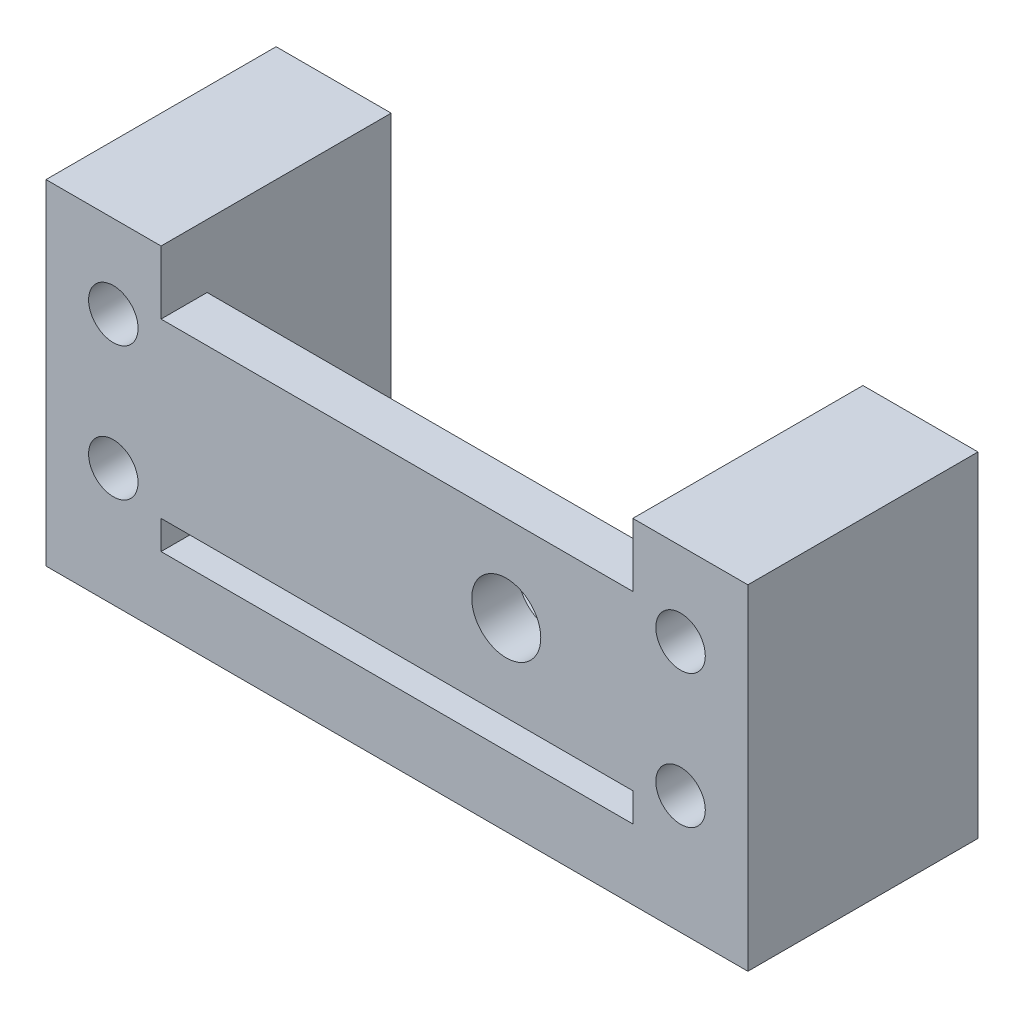
SolidWorks part; units mm, degrees
ref_plane "Спереди" through (0, 0, 0) normal (0, 0, 1) x (1, 0, 0)
ref_plane "Сверху" through (0, 0, 0) normal (0, 1, 0) x (1, 0, 0)
ref_plane "Справа" through (0, 0, 0) normal (1, 0, 0) x (0, 0, -1)
sketch "Эскиз1" plane through (0, 0, 0) normal (0, 0, 1) x (1, 0, 0)
  line L2 (-61.1906, -40.1769) -> (-61.1906, -15.0857)
  line L3 (-61.1906, -15.0857) -> (-51.1906, -15.0857)
  line L4 (-0.1906, -38.0857) -> (-0.1906, -15.0857)
  line L8 (-0.1906, -15.0857) -> (-10.1906, -15.0857)
  line L9 (-10.1906, -15.0857) -> (-10.1906, -38.0857)
  line L10 (-51.1906, -15.0857) -> (-51.1906, -38.0857)
  line L11 (-51.1906, -38.0857) -> (-10.1906, -38.0857)
  line L12 (-61.1906, -40.1769) -> (-61.1906, -44.1769)
  line L13 (-61.1906, -44.1769) -> (-0.1906, -44.1769)
  line L14 (-0.1906, -44.1769) -> (-0.1906, -38.0857)
  point P0 (0, 0)
extrude "Бобышка-Вытянуть1" add sketch "Эскиз1" along normal blind 20
sketch "Эскиз3" plane through (-61.1906, 0, 0) normal (-1, 0, 0) x (0, 0, 1)
  line L5 (0, -15.0857) -> (0, -44.1769) construction
  line L6 (15, -15.0857) -> (0, -15.0857) construction
  line L7 (15, -15.0857) -> (15, -38.2478) construction
  line L8 (15, -38.2478) -> (0, -38.2478) construction
  line L9 (0, -15.0857) -> (0, -38.2478) construction
  point P7 (0, 0)
sketch "Эскиз5" plane through (0, 0, 20) normal (0, 0, 1) x (1, 0, 0)
  line L0 (-51.1906, -38.0857) -> (-51.1906, -15.0857) construction
  line L1 (-10.1906, -28.0857) -> (-24.1906, -28.0857) construction
  line L12 (-10.1906, -38.0857) -> (-51.1906, -38.0857) construction
  line L13 (-10.1906, -38.0857) -> (-10.1906, -18.0857) construction
  line L14 (-10.1906, -18.0857) -> (-51.1906, -18.0857) construction
  line L15 (-51.1906, -38.0857) -> (-51.1906, -18.0857) construction
  line L16 (-21.1906, -35.5857) -> (-51.1906, -35.5857)
  line L18 (-21.1906, -20.5857) -> (-51.1906, -20.5857)
  line L19 (-51.1906, -35.5857) -> (-51.1906, -20.5857)
  line L20 (-21.1906, -20.5857) -> (-10.1906, -20.5857)
  line L22 (-21.1906, -35.5857) -> (-10.1906, -35.5857)
  line L23 (-10.1906, -20.5857) -> (-10.1906, -35.5857)
  circle A5 centre (-21.1906, -28.0857) radius 3
  point P10 (0, 0)
  point P11 (0, 0)
extrude "Бобышка-Вытянуть6" add sketch "Эскиз5" against normal blind 4
sketch "Эскиз6" plane through (0, 0, 20) normal (0, 0, 1) x (1, 0, 0)
  line L0 (-51.1906, -20.5857) -> (-51.1906, -15.0857) construction
  line L1 (-10.1906, -38.0857) -> (-51.1906, -38.0857)
  line L2 (-10.1906, -38.0857) -> (-10.1906, -18.0857)
  line L3 (-10.1906, -18.0857) -> (-51.1906, -18.0857)
  line L4 (-51.1906, -38.0857) -> (-51.1906, -18.0857)
  line L5 (-10.1906, -38.0857) -> (-0.1906, -38.0857)
  line L6 (-0.1906, -44.1769) -> (-0.1906, -15.0857) construction
  line L7 (-6.0406, -38.0857) -> (-6.0406, -29.5857) construction
  line L8 (-10.1906, -35.5857) -> (-6.0406, -35.5857) construction
  line L9 (-10.1906, -18.0857) -> (-0.1906, -18.0857) construction
  line L10 (-6.0406, -18.0857) -> (-6.0406, -26.5857) construction
  line L11 (-6.0406, -22.2857) -> (-10.1906, -22.2857) construction
  line L12 (-30.6906, -38.0857) -> (-30.6906, -18.0857) construction
  circle A1 centre (-6.0406, -33.8857) radius 2.15
  circle A3 centre (-6.0406, -22.2857) radius 2.15
  circle A4 centre (-55.3406, -22.2857) radius 2.15
  circle A5 centre (-55.3406, -33.8857) radius 2.15
extrude "Вырез-Вытянуть2" cut sketch "Эскиз6" against normal through all contours A1 | A3 | A5 | A4 region at (-6.0406, -33.8857, 20) region at (-6.0406, -22.2857, 20) region at (-55.3406, -22.2857, 20) region at (-55.3406, -33.8857, 20)
